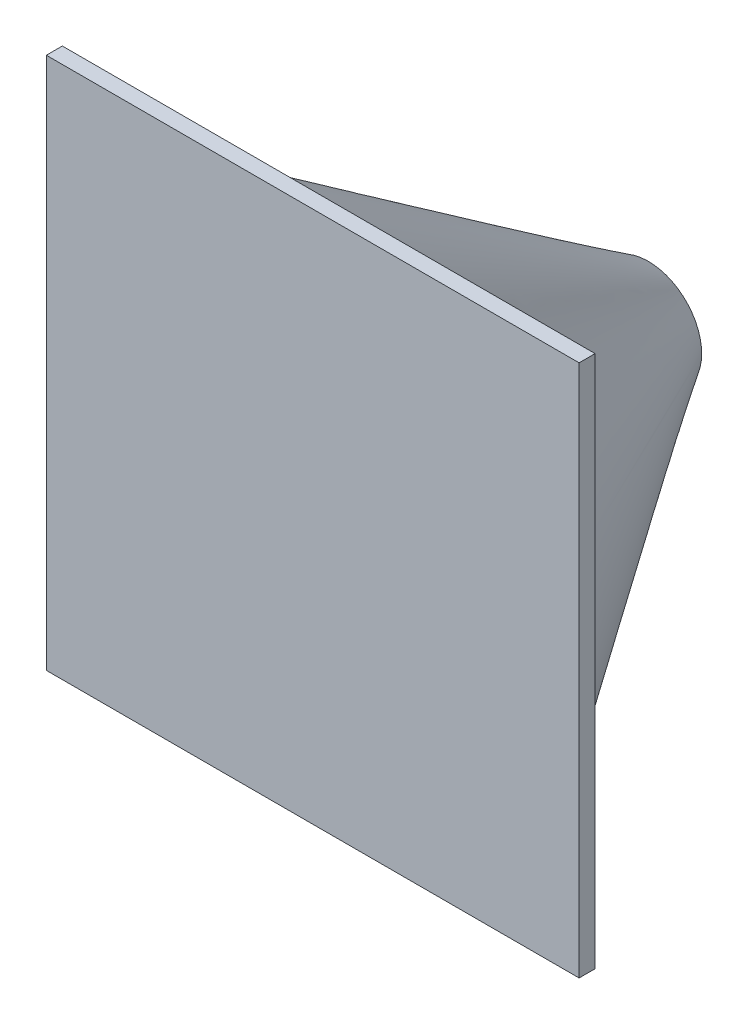
SolidWorks part; units mm, degrees
ref_plane "前视基准面" through (0, 0, 0) normal (0, 0, 1) x (1, 0, 0)
ref_plane "上视基准面" through (0, 0, 0) normal (0, 1, 0) x (1, 0, 0)
ref_plane "右视基准面" through (0, 0, 0) normal (1, 0, 0) x (0, 0, -1)
other "Configuration Table"
sketch "草图2" plane through (0, 0, 0) normal (0, 0, 1) x (1, 0, 0)
  circle A0 centre (0, 0) radius 50
  dimension "D1" = 100
ref_plane "基准面1" through (0, 0, 300) normal (0, 0, 1) x (1, 0, 0)
sketch "草图3" plane through (0, 0, 300) normal (0, 0, 1) x (1, 0, 0)
  circle A0 centre (0, 0) radius 250
  dimension "D1" = 500
loft "放样1" add profiles "草图3", "草图2" connector at (157.2894, 194.3194, 300) connector at (42.3171, 26.632, 0)
sketch "草图4" plane through (0, 0, 300) normal (0, 0, 1) x (1, 0, 0)
  line L0 (0, 250) -> (-250, 250)
  line L1 (-250, 250) -> (-250, -250)
  line L2 (-250, -250) -> (250, -250)
  line L3 (250, -250) -> (250, 250)
  line L4 (250, 250) -> (0, 250)
  circle A0 centre (0, 0) radius 250 construction
  dimension "D1" = 250
  dimension "D2" = 500
  dimension "D3" = 500
extrude "凸台-拉伸1" add sketch "草图4" along normal blind 15
